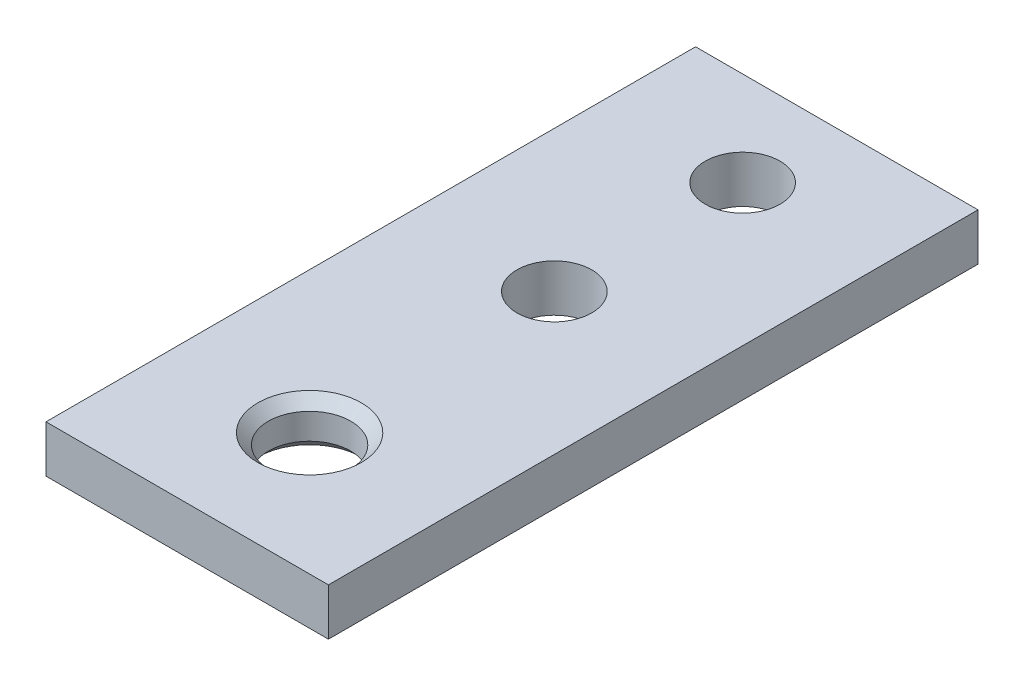
SolidWorks part; units mm, degrees
material "Plain Carbon Steel"
ref_plane "Front Plane" through (0, 0, 0) normal (0, 0, 1) x (1, 0, 0)
ref_plane "Top Plane" through (0, 0, 0) normal (0, 1, 0) x (1, 0, 0)
ref_plane "Right Plane" through (0, 0, 0) normal (1, 0, 0) x (0, 0, -1)
sketch "Sketch1" plane through (0, 0, 0) normal (0, 0, 1) x (1, 0, 0)
  line L1 (-19.05, -3.175) -> (19.05, -3.175)
  line L2 (-19.05, -3.175) -> (-19.05, 3.175)
  line L3 (-19.05, 3.175) -> (19.05, 3.175)
  line L4 (19.05, -3.175) -> (19.05, 3.175)
  line L5 (-19.05, -3.175) -> (19.05, 3.175) construction
  line L6 (-19.05, 3.175) -> (19.05, -3.175) construction
  point P0 (0, 0)
  dimension "D1" = 38.1
  dimension "D2" = 6.35
extrude "Extrude1" add sketch "Sketch1" along normal blind 87.63
sketch "Sketch2" plane through (0, 3.175, 0) normal (0, 1, 0) x (1, 0, 0)
  line L0 (0, 0) -> (0, -12.7) construction
  line L1 (19.05, 0) -> (-19.05, 0) construction
  line L2 (0, -12.7) -> (0, -38.1) construction
  line L3 (0, -38.1) -> (0, -71.12) construction
  line L4 (19.05, -87.63) -> (-19.05, -87.63) construction
  dimension "D1" = 12.7
  dimension "D2" = 38.1
  dimension "D3" = 16.51
hole_wizard "3/8 Clearance Hole1" positions "3DSketch1" profile "Sketch3" hole size "3/8" standard "Ansi Inch"
sketch3d "3DSketch1"
  point P0 (0, 3.175, 12.7)
  point P3 (0, 3.175, 38.1)
sketch "Sketch3" plane through (0, 3.175, 12.7) normal (1, 0, 0) x (0, 0, 1)
  line L0 (0, 0) -> (0, 19.0315)
  line L1 (0, 19.0315) -> (5.0419, 16.002)
  line L2 (5.0419, 16.002) -> (5.0419, 0)
  line L5 (5.0419, 0) -> (0, 0)
  line L10 (0, 19.0315) -> (-5.0419, 16.002) construction
  line L11 (0, -6.35) -> (0, 107.95) construction
  dimension "Hole Dia." = 10.0838
  dimension "Hole Depth" = 16.002
  dimension "Drill Angle" = 118
hole_wizard "7/16 (0.4375) Diameter Hole2" positions "3DSketch2" profile "Sketch4" hole size "7/16" standard "Ansi Inch" end condition through all
sketch3d "3DSketch2"
  point P0 (0, 3.175, 71.12)
sketch "Sketch4" plane through (0, 3.175, 71.12) normal (1, 0, 0) x (0, 0, 1)
  line L0 (0, 0) -> (0, 6.35)
  line L1 (0, 6.35) -> (6.985, 6.35)
  line L2 (5.5562, 4.9212) -> (5.5562, 1.4287)
  line L3 (5.5562, 1.4287) -> (6.985, 0)
  line L5 (6.985, 0) -> (0, 0)
  line L6 (-5.5562, 1.4287) -> (-6.985, 0) construction
  line L7 (6.985, 6.35) -> (5.5562, 4.9212)
  line L8 (-6.985, 6.35) -> (-5.5562, 4.9212) construction
  line L11 (0, -6.35) -> (0, 107.95) construction
  dimension "Thru Hole Dia." = 11.1125
  dimension "Thru Hole Depth" = 6.35
  dimension "Near C'Sink Dia." = 13.97
  dimension "Near C'Sink Angle" = 90
  dimension "Far C'Sink Dia." = 13.97
  dimension "Far C'Sink Angle" = 90
sketch "Sketch5" plane through (0, 3.175, 0) normal (0, 1, 0) x (1, 0, 0)
  line L0 (19.05, -87.63) -> (19.05, 0) construction
  line L1 (-12.2634, -80.7474) -> (19.05, -80.7474)
  line L2 (-12.2634, -80.7474) -> (-12.2634, -64.6781)
  line L3 (-12.2634, -64.6781) -> (19.05, -64.6781)
  line L4 (19.05, -80.7474) -> (19.05, -64.6781)
extrude "Extrude2" [suppressed] add sketch "Sketch5" along normal blind 5.08
